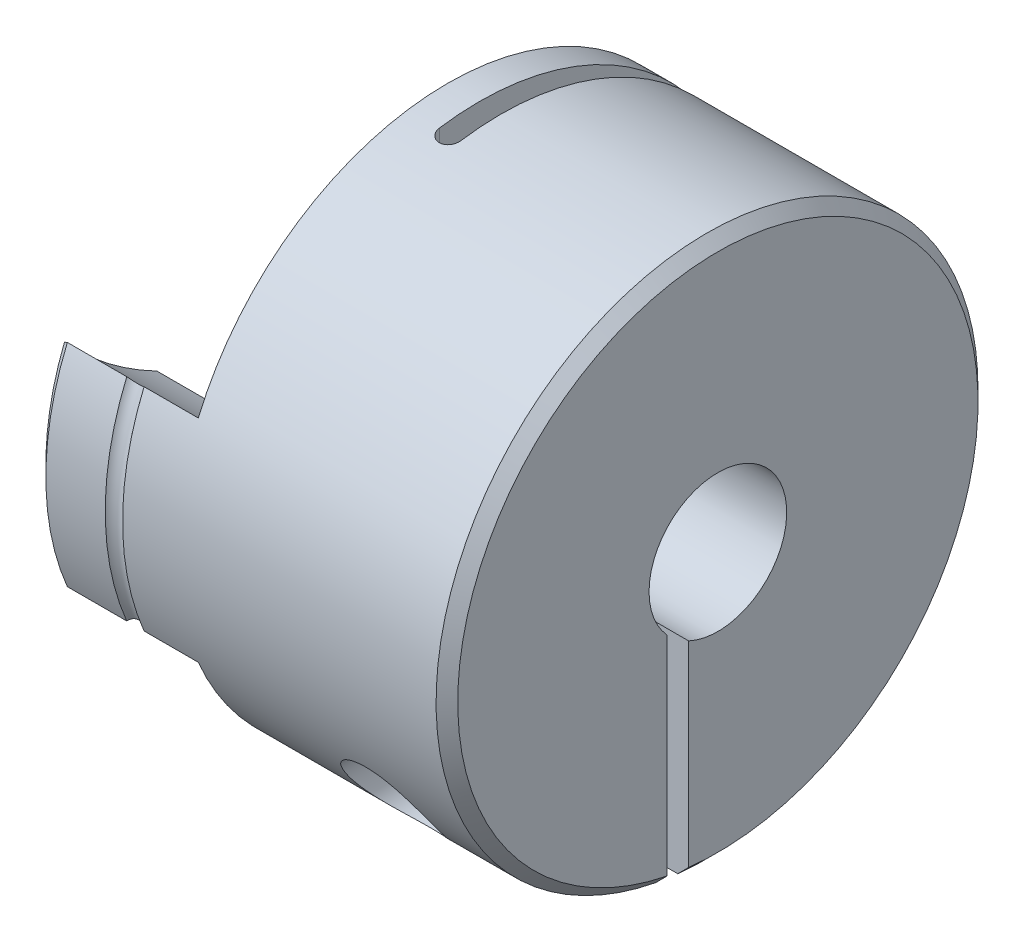
SolidWorks part; units mm, degrees
material "Aluminio"
ref_plane "Front Plane" through (0, 0, 0) normal (0, 0, 1) x (1, 0, 0)
ref_plane "Top Plane" through (0, 0, 0) normal (0, 1, 0) x (1, 0, 0)
ref_plane "Right Plane" through (0, 0, 0) normal (1, 0, 0) x (0, 0, -1)
sketch "Sketch1" plane through (0, 0, 0) normal (1, 0, 0) x (0, 0, -1)
  circle A0 centre (0, 0) radius 12.5
  dimension "D1" = 25
extrude "Boss-Extrude1" add sketch "Sketch1" along normal blind 19
sketch "Sketch3" plane through (0, 0, 0) normal (-1, 0, 0) x (0, 0, 1)
  circle A0 centre (0, 0) radius 6.975
  dimension "D1" = 13.95
extrude "Cut-Extrude1" cut sketch "Sketch3" against normal up to next
ref_axis "Axis1" through (19, 0, 0) along (-1, 0, 0)
ref_plane "Plane1" through (0, 0, 0) normal (0, 1, 0) x (1, 0, 0)
sketch "Sketch2" plane through (0, 0, 0) normal (-1, 0, 0) x (0, 0, 1)
  line L0 (0, -16.2717) -> (0, 15.7546) construction
  line L1 (-19.7237, 0.5) -> (-6.8763, 0.5) construction
  line L2 (-19.7237, -0.5) -> (-6.8763, -0.5) construction
  line L3 (6.8763, 1.169) -> (6.8763, -1.169)
  line L4 (-6.8763, -1.169) -> (-6.8763, 1.169)
  line L5 (6.8763, 0.5) -> (23.5536, 0.5) construction
  line L6 (6.8763, -0.5) -> (23.5536, -0.5) construction
  arc A2 (-6.8763, -1.169) -> (6.8763, -1.169) centre (0, -14.5) ccw
  arc A3 (6.8763, 1.169) -> (-6.8763, 1.169) centre (0, 14.5) ccw
  circle A5 centre (0, 0) radius 6.975 construction
  dimension "D1" = 0.5
  dimension "D2" = 0.5
extrude "Cut-Extrude2" cut sketch "Sketch2" against normal blind 6.54
sketch "Sketch5" plane through (0, 0, 0) normal (0, -1, 0) x (-1, 0, 0)
  line L0 (-19, 0) -> (0, 0) construction
  line L2 (-19, 12.5) -> (-19, -12.5) construction
  circle A0 centre (-3.64, 12.8) radius 0.5
  dimension "D1" = 1
  dimension "D3" = 15.36
  dimension "D2" = 12.8
revolve "Cut-Revolve1" cut sketch "Sketch5" angle 360 about axis through (19, 0, 0) along (-1, 0, 0)
sketch "Sketch6" plane through (0, 0, 0) normal (0, 1, 0) x (1, 0, 0)
  line L0 (8.5, 14.85) -> (8.5, -1.85) construction
  line L1 (9, 14.85) -> (9, -1.85)
  line L2 (8, 14.85) -> (8, -1.85)
  line L4 (19, -12.5) -> (19, 12.5) construction
  line L5 (8, 14.85) -> (9, 14.85)
  arc A1 (8, -1.85) -> (9, -1.85) centre (8.5, -1.85) ccw
  point P2 (13.7613, 6.5)
  dimension "D3" = 16.7
  dimension "D1" = 10
  dimension "D2" = 1
  dimension "D4" = 16.7
extrude "Cut-Extrude4" cut sketch "Sketch6" against normal mid plane 35
sketch "Sketch9" plane through (0, 0, 0) normal (0, 1, 0) x (1, 0, 0)
  line L0 (8.5, -1.85) -> (27.7985, -1.85) construction
  line L1 (8.5, -1.35) -> (27.7985, -1.35)
  line L2 (8.5, -2.35) -> (27.7985, -2.35)
  arc A0 (8.5, -1.35) -> (8.5, -2.35) centre (8.5, -1.85) ccw
  arc A1 (27.7985, -2.35) -> (27.7985, -1.35) centre (27.7985, -1.85) ccw
  point P3 (18.1493, -1.85)
  dimension "D1" = 1
extrude "Cut-Extrude5" cut sketch "Sketch9" against normal blind 15
ref_plane "Plane2" through (0, 0, -13.65) normal (0, 0, 1) x (1, 0, 0)
hole_wizard "Refrentado para tornillo tapón con cabeza de clavija de M2.51" positions "Sketch12" profile "Sketch11" counterbore size "M2.5" standard "Ansi Metric" end condition through all
sketch "Sketch12" plane through (0, 0, -13.65) normal (0, 0, 1) x (1, 0, 0)
  line L0 (19, -12.4269) -> (9, -12.4269) construction
  line L1 (9, 12.5) -> (9, -12.5) construction
  point P0 (14, -7.4269)
  dimension "D1" = 5
  dimension "D2" = 5
sketch "Sketch11" plane through (14, -7.4269, -13.65) normal (1, 0, 0) x (0, 1, 0)
  line L0 (0, 0) -> (0, 26.15)
  line L1 (0, 26.15) -> (1.955, 26.15)
  line L3 (1.955, 26.15) -> (1.955, 8)
  line L4 (1.955, 8) -> (3.25, 8)
  line L5 (3.25, 8) -> (3.25, 0)
  line L7 (3.25, 0) -> (0, 0)
  line L11 (0, -6.35) -> (0, 107.95) construction
  dimension "Thru Hole Dia." = 3.91
  dimension "Thru Hole Depth" = 26.15
  dimension "C'Bore Dia." = 6.5
  dimension "C'Bore Depth" = 8
ref_axis "Eje1" through (14, -7.4269, 1.8274) along (0, 0, -1)
ref_plane "Plano1" through (0, 0, -5.65) normal (0, 0, -1) x (-1, 0, 0)
ref_plane "Plano2" through (0, -7.4269, 0) normal (0, 1, 0) x (1, 0, 0)
chamfer "Chaflán1" distance 0.5 angle 45 3 edges at (19, 12.3621, -1.8515) (0, 0, -12.5) (0, 0, 12.5)
sketch "Szkic1" plane through (19, 0, 0) normal (1, 0, 0) x (0, 0, -1)
  line L0 (-2.35, -6.5672) -> (-2.35, -2.135)
  line L1 (-1.35, -6.8431) -> (-1.35, -2.8737)
  arc A0 (-1.35, -6.8431) -> (-2.35, -6.5672) centre (0, 0) ccw construction
  arc A1 (-1.35, -6.8431) -> (-2.35, -6.5672) centre (0, 0) ccw
  arc A2 (-1.35, -2.8737) -> (-2.35, -2.135) centre (0, 0) ccw
  dimension "D1" = 6.35
extrude "Dodanie-wyciągnięcie1" add sketch "Szkic1" against normal up to surface (10 mm away) up to face at (9, 0.1044, -4.0669)
